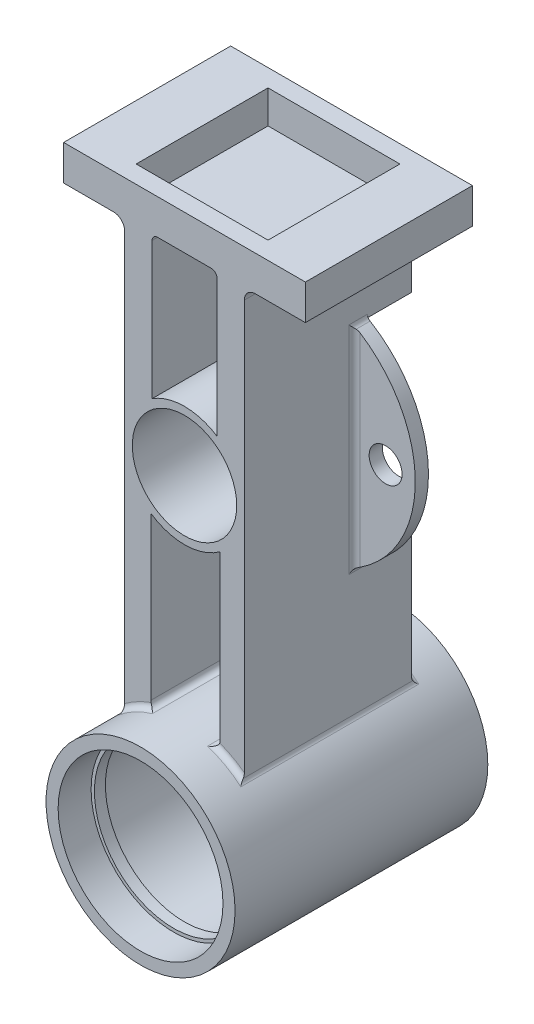
SolidWorks part; units mm, degrees
material "PLA"
ref_plane "Alzado" through (0, 0, 0) normal (0, 0, 1) x (1, 0, 0)
ref_plane "Planta" through (0, 0, 0) normal (0, 1, 0) x (1, 0, 0)
ref_plane "Vista lateral" through (0, 0, 0) normal (1, 0, 0) x (0, 0, -1)
sketch "Croquis1" plane through (0, 0, 0) normal (0, 0, 1) x (1, 0, 0)
  circle A0 centre (0, 0) radius 11
  circle A2 centre (0, 0) radius 4.75
  circle A3 centre (8.3, 0) radius 1.5
  circle A4 centre (0, -8.3) radius 1.5
  circle A5 centre (-8.3, 0) radius 1.5
  point P19 (0, 0)
  dimension "D1" = 22
  dimension "D3" = 9.5
extrude "Saliente-Extruir1" add sketch "Croquis1" along normal blind 1.2
sketch "Croquis2" plane through (0, 0, 1.2) normal (0, 0, 1) x (1, 0, 0)
  line L0 (-5.45, 0) -> (-5.45, 17.55)
  line L1 (-11, 17.55) -> (-5.45, 17.55)
  line L2 (5.45, 17.55) -> (5.45, 0)
  line L3 (-2.95, 4.5826) -> (-2.95, 17.55)
  line L4 (11, 17.55) -> (11, 20.75)
  line L5 (11, 20.75) -> (-11, 20.75)
  line L6 (-11, 20.75) -> (-11, 17.55)
  line L7 (5.45, 17.55) -> (11, 17.55)
  line L8 (2.95, 4.5826) -> (2.95, 17.55)
  line L13 (-2.95, 17.55) -> (-1.25, 17.55)
  line L14 (1.25, 17.55) -> (2.95, 17.55)
  line L15 (-1.25, 17.55) -> (1.25, 17.55)
  arc A0 (-5.45, 0) -> (5.45, 0) centre (0, 0) ccw
  circle A1 centre (0, 0) radius 4.75 construction
  circle A2 centre (0, 0) radius 4.75
  arc A3 (-5.45, 0) -> (5.45, 0) centre (0, 0) ccw
  arc A4 (2.95, 4.5826) -> (1.1848, 5.3197) centre (0, 0) ccw
  arc A5 (-1.1848, 5.3197) -> (-2.95, 4.5826) centre (0, 0) ccw
  arc A6 (-5.45, 0) -> (5.45, 0) centre (0, 0) ccw
  arc A7 (2.95, 4.5826) -> (-2.95, 4.5826) centre (0, 0) ccw
  point P1 (0, 20.75)
  circle M4 centre (0, 0) radius 4.75
  circle M5 centre (0, 0) radius 11
  dimension "D1" = 0.7
  dimension "D2" = 2.5
  dimension "D3" = 3.2
  dimension "D4" = 22
  dimension "D6" = 2.5
extrude "Saliente-Extruir2" add sketch "Croquis2" along normal blind 10 and the other way blind 1.2 contours L13 L15 L14 L8 L2 L7 L4 L5 L6 L1 L0 L3 M5 | A4 A7 A5 L3 L0 A0 L2 L8 M5 M4 region at (-5.256, 4.7775, 1.2) region at (-5.2032, 13.5525, 1.2)
sketch "Croquis5" plane through (0, 0, 0) normal (0, 0, -1) x (-1, 0, 0)
  line L0 (-5.45, 9.555) -> (-5.45, 17.55)
  line L1 (-5.45, 17.55) -> (-11, 17.55)
  line L2 (-11, 17.55) -> (-11, 20.75)
  line L3 (-11, 20.75) -> (11, 20.75)
  line L4 (11, 20.75) -> (11, 17.55)
  line L5 (11, 17.55) -> (5.45, 17.55)
  line L6 (5.45, 17.55) -> (5.45, 9.555)
  line L7 (-2.95, 10.5971) -> (-2.95, 17.55)
  line L8 (-2.95, 17.55) -> (-1.25, 17.55)
  line L9 (-1.25, 17.55) -> (-1.25, 10.9287)
  line L10 (1.25, 10.9287) -> (1.25, 17.55)
  line L11 (1.25, 17.55) -> (2.95, 17.55)
  line L12 (2.95, 17.55) -> (2.95, 10.5971)
  arc A1 (5.45, 9.555) -> (-5.45, 9.555) centre (0, 0) ccw
  line M21 (-5.45, 17.55) -> (-5.45, 9.555)
  line M22 (5.45, 9.555) -> (5.45, 17.55)
  line M23 (-2.95, 17.55) -> (2.95, 17.55)
  line M24 (11, 17.55) -> (11, 20.75)
  line M25 (11, 20.75) -> (-11, 20.75)
  line M26 (-11, 20.75) -> (-11, 17.55)
  line M30 (5.45, 17.55) -> (11, 17.55)
  line M31 (2.95, 17.55) -> (2.95, 10.5971)
  line M33 (-2.95, 10.5971) -> (-2.95, 17.55)
  line M36 (-11, 17.55) -> (-5.45, 17.55)
extrude "Saliente-Extruir3" add sketch "Croquis5" along normal blind 4 contours A1 M22 M30 M24 M25 M26 M36 M21 M33 M23 M31 region at (5.2032, 13.5525, 0)
fillet "Redondeo1" radius 1 2 edges at (-5.45, 17.55, 3.6) (5.45, 17.55, 3.6)
sketch "Croquis3" plane through (0, 20.75, 0) normal (0, 1, 0) x (1, 0, 0)
  line L0 (11, -11.2) -> (11, 4) construction
  line L1 (-6, -9.6) -> (6, -9.6)
  line L2 (-6, -9.6) -> (-6, 2.4)
  line L3 (-6, 2.4) -> (6, 2.4)
  line L4 (6, -9.6) -> (6, 2.4)
  line L5 (-6, -9.6) -> (6, 2.4) construction
  line L6 (-6, 2.4) -> (6, -9.6) construction
  point P0 (0, -3.6)
  point P7 (11, -3.6)
  dimension "D1" = 12
  dimension "D2" = 12
extrude "Cortar-Extruir1" cut sketch "Croquis3" against normal blind 3
sketch "Croquis6" plane through (0, 0, 0) normal (0, 0, 1) x (1, 0, 0)
  line L0 (0, -4.3821) -> (0, -19.3821) construction
  line L1 (-5.45, 0) -> (-5.45, -21.3294)
  line L2 (5.45, 0) -> (5.45, -21.3294)
  line L3 (-3.0713, -4.5022) -> (-3.0713, -19.9492)
  line L4 (3.2404, -4.3821) -> (3.2404, -20.0159)
  line L5 (1.5, -8.3) -> (1.5, -12.6162) construction
  line L6 (-1.5, -8.3) -> (-1.5, -12.6162) construction
  line L7 (0, -4.3821) -> (5.0391, -4.3821) construction
  line L8 (0, -11) -> (5.45, -11) construction
  circle A0 centre (0, -27.9821) radius 7.5
  arc A1 (-5.45, -21.3294) -> (5.45, -21.3294) centre (0, -27.9821) ccw
  arc A2 (-5.45, 9.555) -> (5.45, 9.555) centre (0, 0) ccw construction
  arc A3 (-5.45, 0) -> (5.45, 0) centre (0, 0) ccw construction
  circle A4 centre (0, -8.3) radius 1.5 construction
  arc A5 (-5.45, 0) -> (-3.0713, -4.5022) centre (0, 0) ccw
  arc A6 (3.2404, -20.0159) -> (-3.0713, -19.9492) centre (0, -27.9821) ccw
  arc A7 (3.2404, -4.3821) -> (5.45, 0) centre (0, 0) ccw
  circle A8 centre (0, -27.9821) radius 8.6
  dimension "D1" = 15
  dimension "D2" = 1.1
  dimension "D4" = 1.7404
  dimension "D3" = 15
extrude "Saliente-Extruir4" add sketch "Croquis6" along normal blind 15.2 and the other way blind 7.8 separate body contours A1 A8 A6 A0 region at (-4.1941, -20.754, 0)
extrude "Saliente-Extruir5" add sketch "Croquis6<3>" along normal blind 11.2 contours A8 L2 A7 L4 | A8 L3 A5 L1 region at (-4.3158, -11.8321, 0) region at (4.3945, -11.8063, 0)
sketch "Croquis6<3>" plane through (0, 0, 0) normal (0, 0, 1) x (1, 0, 0) same geometry as "Croquis6"
sketch "Croquis9" plane through (0, 0, 0) normal (0, 0, -1) x (-1, 0, 0)
  line L0 (-5.45, -9.555) -> (-5.45, -21.3294)
  line L1 (3.0713, -11.5542) -> (3.0713, -19.9492)
  line L2 (5.45, -9.555) -> (5.45, -21.3294)
  line L3 (-3.2404, -11.5542) -> (-3.2404, -20.0159)
  line L4 (-3.2404, -11.5542) -> (-3.2404, -10.5119)
  line L5 (3.0713, -11.5542) -> (3.0713, -10.5625)
  arc A1 (-3.2404, -20.0159) -> (-5.45, -21.3294) centre (0, -27.9821) ccw
  arc A3 (5.45, -21.3294) -> (3.0713, -19.9492) centre (0, -27.9821) ccw
  arc A7 (-5.45, -9.555) -> (-3.2404, -10.5119) centre (0, 0) ccw
  arc A8 (3.0713, -10.5625) -> (5.45, -9.555) centre (0, 0) ccw
extrude "Saliente-Extruir8" add sketch "Croquis9" along normal blind 4
sketch "Croquis10" plane through (0, 0, 0) normal (0, 0, -1) x (-1, 0, 0)
  line L0 (-4.23, -10.3031) -> (-4.23, -11.1603)
  line L1 (4.23, -10.3031) -> (4.23, -11.1603)
  arc A0 (-4.1647, -11.2541) -> (4.1647, -11.2541) centre (0, 0) ccw
  arc A1 (-4.0928, -10.2103) -> (4.0928, -10.2103) centre (0, 0) ccw
  arc A3 (4.23, -11.1603) -> (4.1647, -11.2541) centre (4.13, -11.1603) cw
  arc A4 (4.23, -10.3031) -> (4.0928, -10.2103) centre (4.13, -10.3031) ccw
  arc A5 (-4.23, -10.3031) -> (-4.0928, -10.2103) centre (-4.13, -10.3031) cw
  arc A6 (-4.23, -11.1603) -> (-4.1647, -11.2541) centre (-4.13, -11.1603) ccw
  dimension "D1" = 1
  dimension "D2" = 0.1
extrude "Saliente-Extruir13" add sketch "Croquis10" along normal blind 4 and the other way blind 1.2
sketch "Croquis11" plane through (0, 0, -4) normal (0, 0, -1) x (-1, 0, 0)
  line L0 (-1.25, -11.9347) -> (-1.25, -19.4734)
  line L1 (-1.25, -11.9347) -> (1.25, -11.9347) construction
  line L2 (1.25, -11.9347) -> (1.25, -19.4734)
  line L5 (-1.25, -19.4734) -> (1.25, -19.4734)
  line L6 (-1.25, -11.9347) -> (1.25, -11.9347)
  arc A0 (-3.2404, -11.5542) -> (3.0713, -11.6003) centre (0, 0) ccw construction
  circle A1 centre (0, -27.9821) radius 8.6 construction
  circle A2 centre (0, -27.9821) radius 8.6 construction
  point P7 (0, -11.9347)
  dimension "D1" = 2.5
extrude "Saliente-Extruir14" add sketch "Croquis11" against normal blind 5.2
sketch "Croquis12" plane through (0, 0, 15.2) normal (0, 0, 1) x (1, 0, 0)
  circle A0 centre (0, -27.9821) radius 7.9526
  circle A1 centre (0, -27.9821) radius 7.2
  circle A2 centre (0, -27.9821) radius 7.5 construction
  dimension "D1" = 0.3
extrude "Saliente-Extruir15" add sketch "Croquis12" against normal blind 1 from offset 3 offset against normal yes
sketch "Croquis14" plane through (0, 0, 1.2) normal (0, 0, 1) x (1, 0, 0)
  line L2 (1.25, 17.55) -> (1.25, 10.9287) construction
  line L3 (-1.25, 10.9287) -> (-1.25, 17.55) construction
  line L6 (-1.25, 17.55) -> (1.25, 17.55)
  line L7 (-3.737, 10.3457) -> (-3.737, 11.4033)
  line L8 (3.737, 10.3457) -> (3.737, 11.4033)
  line L22 (1.25, 17.55) -> (1.25, 11.9347)
  line L23 (-1.25, 11.9347) -> (-1.25, 17.55)
  arc A0 (1.25, 10.9287) -> (-1.25, 10.9287) centre (0, 0) ccw
  arc A1 (3.737, 10.3457) -> (-3.737, 10.3457) centre (0, 0) ccw
  arc A3 (3.737, 11.4033) -> (1.25, 11.9347) centre (0, 0) ccw
  arc A4 (-1.25, 11.9347) -> (-3.737, 11.4033) centre (0, 0) ccw
  arc M11 (2.95, 10.5971) -> (-2.95, 10.5971) centre (0, 0) ccw
  dimension "D1" = 1
extrude "Saliente-Extruir16" add sketch "Croquis14" against normal blind 5.2 contours L23 A4 L7 A1 L8 A3 L22 L6 M11 region at (0, 13.5367, 1.2)
sketch "Croquis15" plane through (0, 0, 0) normal (0, 0, -1) x (-1, 0, 0)
  circle A2 centre (0, 8.3) radius 1.5
  point P12 (0, 0)
extrude "Cortar-Extruir2" cut sketch "Croquis15" against normal blind 5.2
fillet "Redondeo2" radius 0.5 27 edges at (2.95, 17.55, 3.6) (-2.95, 17.55, 3.6) (-1.25, 17.55, -1.4) (1.25, 17.55, -1.4) (5.45, 0, 1.2) (-5.45, 0, 1.2) (-5.45, -9.555, 0.6) (5.45, -9.555, 0.6) (5.45, 9.555, 0.6) (-5.45, 9.555, 0.6) (4.3945, -20.5896, 11.2) (4.3945, -20.5896, -4) (-4.3162, -20.5436, -4) (-4.3162, -20.5436, 11.2) (-5.45, -21.3294, 3.6) (5.45, -21.3294, 3.6) (3.2404, -20.0159, 3.6) (-3.0713, -19.9492, 3.6) (1.25, -19.4734, -1.4) (3.2404, -11.5542, -1.4) (-1.25, -11.9347, -1.4) (-3.0713, -11.6003, -1.4) (1.25, -11.9347, -1.4) (2.95, 11.6317, -1.4) (1.25, 11.9347, -1.4) (-1.25, 11.9347, -1.4) (-2.95, 11.6317, -1.4)
